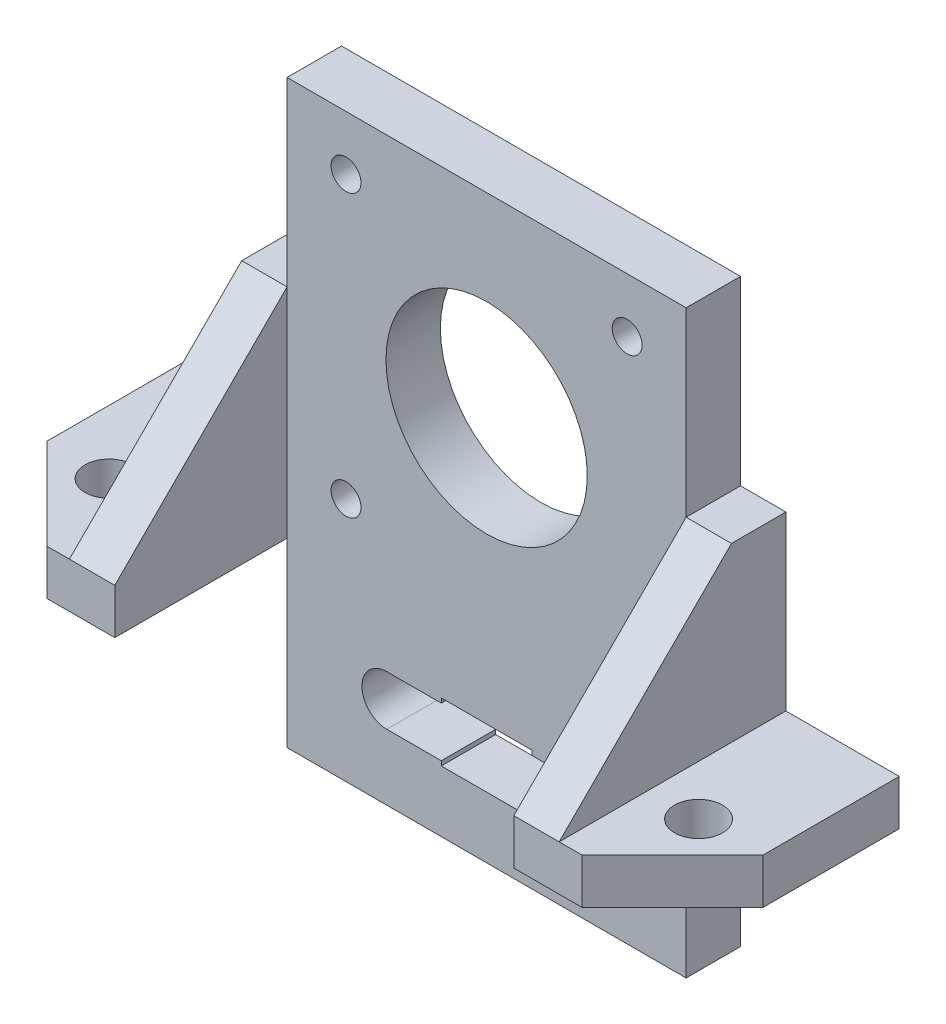
SolidWorks part; units mm, degrees
ref_plane "Plano frontal" through (0, 0, 0) normal (0, 0, 1) x (1, 0, 0)
ref_plane "Plano superior" through (0, 0, 0) normal (0, 1, 0) x (1, 0, 0)
ref_plane "Plano direito" through (0, 0, 0) normal (1, 0, 0) x (0, 0, -1)
sketch "Esboço1" plane through (0, 0, 0) normal (0, 0, 1) x (1, 0, 0)
  line L16 (39.5, -17.5) -> (39.5, -22.5)
  line L17 (22, 1.5) -> (27, 1.5)
  line L18 (27, 1.5) -> (27, -17.5)
  line L19 (27, -17.5) -> (39.5, -17.5)
  line L20 (39.5, -22.5) -> (22, -22.5)
  line L21 (22, -22.5) -> (22, -42.5)
  line L22 (22, -42.5) -> (-22, -42.5)
  line L23 (-22, -42.5) -> (-22, -22.5)
  line L24 (-22, -22.5) -> (-39.5, -22.5)
  line L25 (-39.5, -22.5) -> (-39.5, -17.5)
  line L26 (-39.5, -17.5) -> (-27, -17.5)
  line L27 (-27, -17.5) -> (-27, 1.5)
  line L28 (-27, 1.5) -> (-22, 1.5)
  line L29 (-22, 1.5) -> (-22, 21.5)
  line L30 (-22, 21.5) -> (22, 21.5)
  line L31 (22, 21.5) -> (22, 1.5)
  line L42 (-5, -35.25) -> (-5, -35.75)
  line L43 (-11, -35.25) -> (-5, -35.25)
  line L44 (-5, -29.75) -> (-11, -29.75)
  line L45 (-5, -29.25) -> (-5, -29.75)
  line L46 (5, -29.75) -> (5, -29.25)
  line L47 (5, -35.75) -> (5, -35.25)
  line L48 (-5, -35.75) -> (5, -35.75)
  line L49 (5, -29.25) -> (-5, -29.25)
  line L50 (5, -35.25) -> (11, -35.25)
  line L51 (11, -29.75) -> (5, -29.75)
  line L52 (-15.5, 15.5) -> (15.5, -15.5) construction
  line L53 (-15.5, -15.5) -> (15.5, 15.5) construction
  circle A0 centre (15.5, 15.5) radius 1.65
  arc A1 (-11, -35.25) -> (-11, -29.75) centre (-11, -32.5) cw
  circle A2 centre (15.5, -15.5) radius 1.65
  circle A3 centre (-15.5, 15.5) radius 1.65
  circle A4 centre (-15.5, -15.5) radius 1.65
  circle A5 centre (0, 0) radius 11.1
  arc A6 (11, -35.25) -> (11, -29.75) centre (11, -32.5) ccw
  dimension "D1" = 22.2
  dimension "D2" = 3.3
  dimension "D20" = 11
  dimension "D3" = 31
  dimension "D4" = 31
  dimension "D5" = 44
  dimension "D6" = 20
  dimension "D7" = 5
  dimension "D8" = 19
  dimension "D9" = 12.5
  dimension "D10" = 5
  dimension "D11" = 17.5
  dimension "D12" = 20
  dimension "D13" = 44
  dimension "D14" = 6
  dimension "D15" = 6.5
  dimension "D16" = 10
  dimension "D17" = 0.5
  dimension "D18" = 6
  dimension "D19" = 6.75
  dimension "D21" = 6.5
extrude "Ressalto-extrusão1" add sketch "Esboço1" along normal blind 6
sketch "Esboço2" plane through (0, 0, 6) normal (0, 0, 1) x (1, 0, 0)
  line L0 (39.5, -22.5) -> (39.5, -17.5) construction
  line L1 (39.5, -17.5) -> (27, -17.5) construction
  line L2 (22, -22.5) -> (39.5, -22.5) construction
  line L3 (27, -17.5) -> (27, 1.5) construction
  line L4 (27, 1.5) -> (22, 1.5) construction
  line L5 (-39.5, -22.5) -> (-22, -22.5) construction
  line L6 (-22, 1.5) -> (-27, 1.5) construction
  line L7 (-27, 1.5) -> (-27, -17.5) construction
  line L8 (-39.5, -17.5) -> (-39.5, -22.5) construction
  line L9 (-27, -17.5) -> (-39.5, -17.5) construction
  line L10 (39.5, -22.5) -> (39.5, -17.5)
  line L11 (39.5, -17.5) -> (27, -17.5)
  line L12 (22, -22.5) -> (39.5, -22.5)
  line L13 (27, -17.5) -> (27, 1.5)
  line L14 (27, 1.5) -> (22, 1.5)
  line L15 (-39.5, -22.5) -> (-22, -22.5)
  line L16 (-22, 1.5) -> (-27, 1.5)
  line L17 (-27, 1.5) -> (-27, -17.5)
  line L18 (-39.5, -17.5) -> (-39.5, -22.5)
  line L19 (-27, -17.5) -> (-39.5, -17.5)
  line L20 (-22, 1.5) -> (-22, -22.5)
  line L21 (22, 1.5) -> (22, -22.5)
extrude "Ressalto-extrusão2" add sketch "Esboço2" along normal blind 19
chamfer "Chanfro1" distance 10 angle 45 2 edges at (39.5, -20, 25) (-39.5, -20, 25)
chamfer "Chanfro2" distance 19 angle 45 2 edges at (-24.5, 1.5, 25) (24.5, 1.5, 25)
sketch "Esboço3" plane through (0, -22.5, 0) normal (0, -1, 0) x (1, 0, 0)
  line L0 (39.5, 15) -> (39.5, 0) construction
  line L1 (22, 25) -> (29.5, 25) construction
  line L2 (-39.5, 15) -> (-39.5, 0) construction
  circle A0 centre (32.5, 15.13) radius 2.65
  circle A1 centre (-32.5, 15.13) radius 2.65
  dimension "D1" = 5.3
  dimension "D2" = 7
  dimension "D3" = 9.87
  dimension "D4" = 7
extrude "Corte-extrusão1" cut sketch "Esboço3" against normal up to next
sketch "Esboço4" plane through (0, 0, 0) normal (0, 0, -1) x (-1, 0, 0)
  circle A0 centre (0, 0) radius 11.1 construction
  circle A1 centre (0, 0) radius 11.1
  circle A2 centre (0, 0) radius 16
  dimension "D1" = 32
extrude "Ressalto-extrusão3" [suppressed] add sketch "Esboço4" along normal blind 40
sketch "Esboço5" [suppressed] plane through (0, 0, -40) normal (0, 0, -1) x (-1, 0, 0)
  circle A0 centre (0, 0) radius 11.1 construction
  circle A1 centre (0, 0) radius 11.1
  circle A2 centre (0, 0) radius 5
  dimension "D1" = 10
extrude "Ressalto-extrusão4" [suppressed] add sketch "Esboço5" against normal blind 3 from offset 7 offset against normal yes
ref_axis "Eixo1" [suppressed] through (0, 0, -33) along (0, 0, -1)
ref_plane "Plano1" [suppressed] through (0, 0, 0) normal (0.7071, 0.7071, 0) x (0, 0, -1)
sketch "Esboço6" [suppressed] plane through (0, 0, 0) normal (0.7071, 0.7071, 0) x (0.7071, -0.7071, 0)
  line L0 (0, 24) -> (0, 6) construction
  line L1 (4, 24) -> (4, 6)
  line L2 (-4, 24) -> (-4, 6)
  line L3 (16, 40) -> (-16, 40) construction
  arc A0 (4, 24) -> (-4, 24) centre (0, 24) ccw
  arc A1 (-4, 6) -> (4, 6) centre (0, 6) ccw
  point P3 (0, 15)
  dimension "D3" = 4
  dimension "D1" = 6
  dimension "D2" = 16
extrude "Corte-extrusão5" [suppressed] cut sketch "Esboço6" against normal through all
sketch "Esboço7" [suppressed] plane through (0, 0, 0) normal (1, 0, 0) x (0, 0, -1)
  line L1 (0, -21.5) -> (20, -16)
  line L2 (0, -42.5) -> (0, -22.5) construction
  line L4 (0, -21.5) -> (0, -11.1)
  line L7 (40, -16) -> (0, -16) construction
  line L8 (40, -16) -> (40, 16) construction
  line L9 (0, -17.5) -> (0, 1.5) construction
  line L10 (40, -11.1) -> (0, -11.1) construction
  line L11 (40, -11.1) -> (40, 11.1) construction
  line L12 (20, -16) -> (37.8182, -11.1)
  line L13 (37.8182, -11.1) -> (0, -11.1)
  dimension "D1" = 5.5
  dimension "D2" = 20
extrude "Ressalto-extrusão6" [suppressed] add sketch "Esboço7" along normal blind 3 and the other way blind 3 contours L1 L12 L13 L4
pattern_circular "PadrãoCircular1" [suppressed] count 4 every 90 of bodies 109
